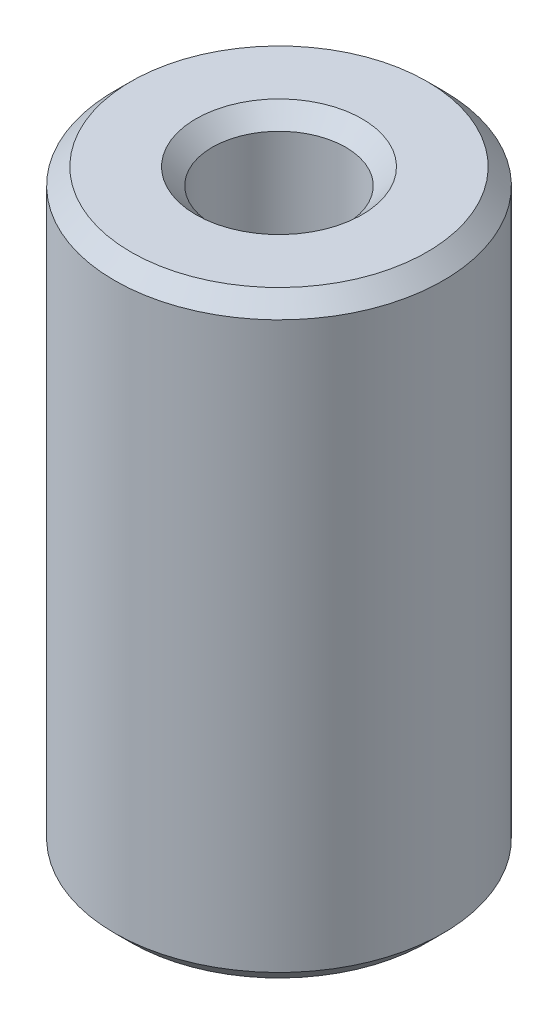
SolidWorks part; units mm, degrees
ref_plane "Front Plane" through (0, 0, 0) normal (0, 0, 1) x (1, 0, 0)
ref_plane "Top Plane" through (0, 0, 0) normal (0, 1, 0) x (1, 0, 0)
ref_plane "Right Plane" through (0, 0, 0) normal (1, 0, 0) x (0, 0, -1)
sketch "Sketch1" plane through (0, 0, 0) normal (0, 1, 0) x (1, 0, 0)
  circle A0 centre (0, 0) radius 7.5
  dimension "SLEEVE_OD" = 15
extrude "Boss-Extrude1" add sketch "Sketch1" along normal blind 27.2913
sketch "Sketch2" plane through (0, 0, 0) normal (0, 1, 0) x (1, 0, 0)
  circle A0 centre (0, 0) radius 3.0437
  dimension "BORE_D" = 6.0874
extrude "Cut-Extrude1" cut sketch "Sketch2" along normal through all
chamfer "Chamfer1" distance 0.7489 angle 45 4 edges at (0, 27.2913, 3.0437) (0, 0, 3.0437) (0, 0, 7.5) (0, 27.2913, 7.5)
